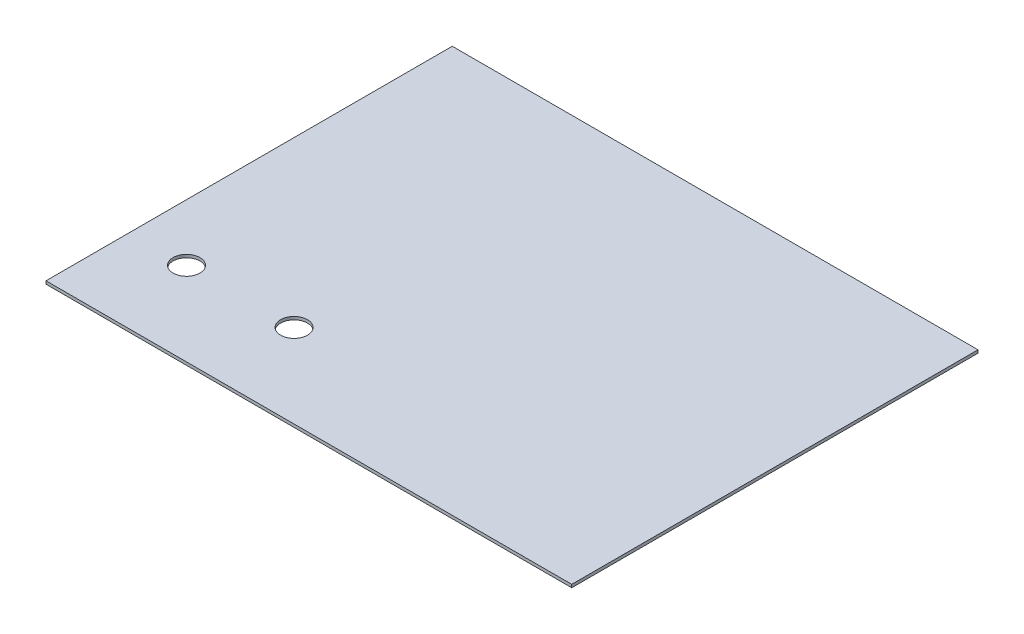
SolidWorks part; units mm, degrees
ref_plane "Front Plane" through (0, 0, 0) normal (0, 0, 1) x (1, 0, 0)
ref_plane "Top Plane" through (0, 0, 0) normal (0, 1, 0) x (1, 0, 0)
ref_plane "Right Plane" through (0, 0, 0) normal (1, 0, 0) x (0, 0, -1)
sketch "Sketch1" plane through (0, 0, 0) normal (0, 1, 0) x (1, 0, 0)
  line L1 (0, 0) -> (558.8, 0)
  line L2 (0, 0) -> (0, 431.8)
  line L3 (0, 431.8) -> (558.8, 431.8)
  line L4 (558.8, 0) -> (558.8, 431.8)
  dimension "D1" = 558.8
  dimension "D2" = 431.8
extrude "Boss-Extrude1" add sketch "Sketch1" along normal blind 3.175
sketch "Sketch2" plane through (0, 3.175, 0) normal (0, 1, 0) x (1, 0, 0)
  line L3 (60.4606, 88.9) -> (174.7606, 88.9) construction
  line L4 (0, 0) -> (558.8, 0) construction
  circle A2 centre (60.4606, 88.9) radius 14.2875
  circle A3 centre (174.7606, 88.9) radius 14.2875
  dimension "D3" = 28.575
  dimension "D4" = 28.575
  dimension "D5" = 114.3
  dimension "D8" = 88.9
extrude "Cut-Extrude1" cut sketch "Sketch2" against normal blind 3.175
